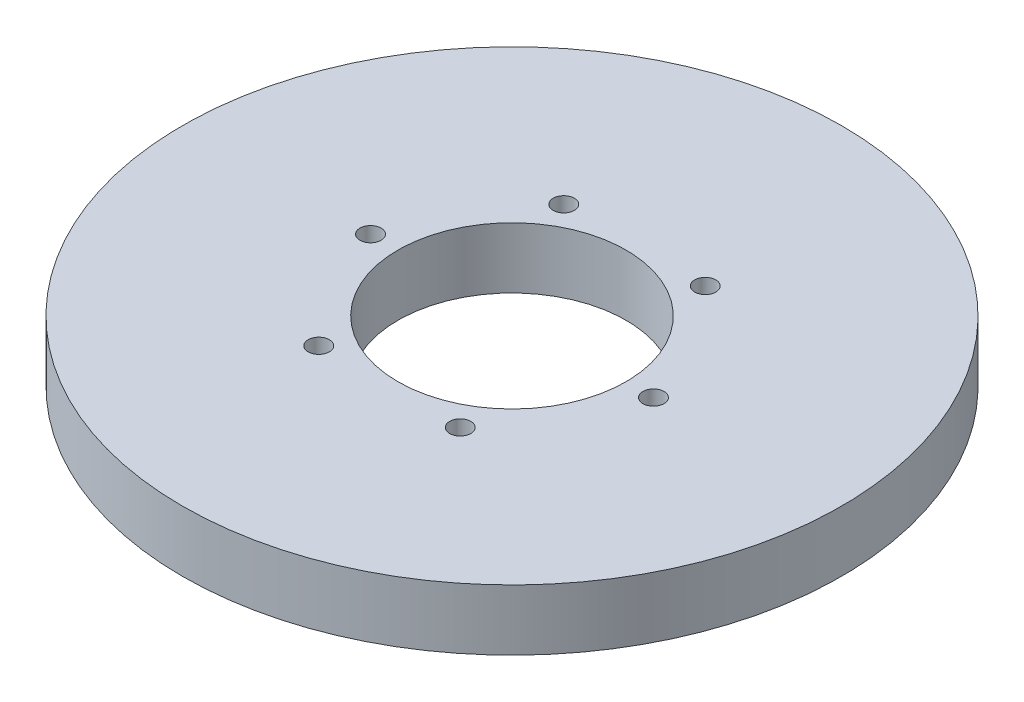
SolidWorks part; units mm, degrees
ref_plane "Front Plane" through (0, 0, 0) normal (0, 0, 1) x (1, 0, 0)
ref_plane "Top Plane" through (0, 0, 0) normal (0, 1, 0) x (1, 0, 0)
ref_plane "Right Plane" through (0, 0, 0) normal (1, 0, 0) x (0, 0, -1)
sketch "Sketch1" plane through (0, 0, 0) normal (0, 1, 0) x (1, 0, 0)
  circle A0 centre (0, 0) radius 65
  dimension "FLANGE_OD" = 130
extrude "Boss-Extrude1" add sketch "Sketch1" along normal blind 12
sketch "Sketch2" plane through (0, 0, 0) normal (0, 1, 0) x (1, 0, 0)
  circle A0 centre (0, 0) radius 22.5
  dimension "BORE_D" = 45
extrude "Cut-Extrude1" cut sketch "Sketch2" along normal through all
sketch "Sketch3" plane through (0, 12, 0) normal (0, 1, 0) x (1, 0, 0)
  circle A0 centre (0, 0) radius 27.902 construction
  circle A1 centre (-27.902, 0) radius 2.0871
  dimension "BOLT_D" = 4.1743
  dimension "BOLT_PCD" = 55.804
extrude "Cut-Extrude2" cut sketch "Sketch3" against normal blind 11.2601
pattern_circular "CirPattern1" count 6 over 360 about axis through (0, 0, 0) along (0, 1, 0) of "Cut-Extrude2"
